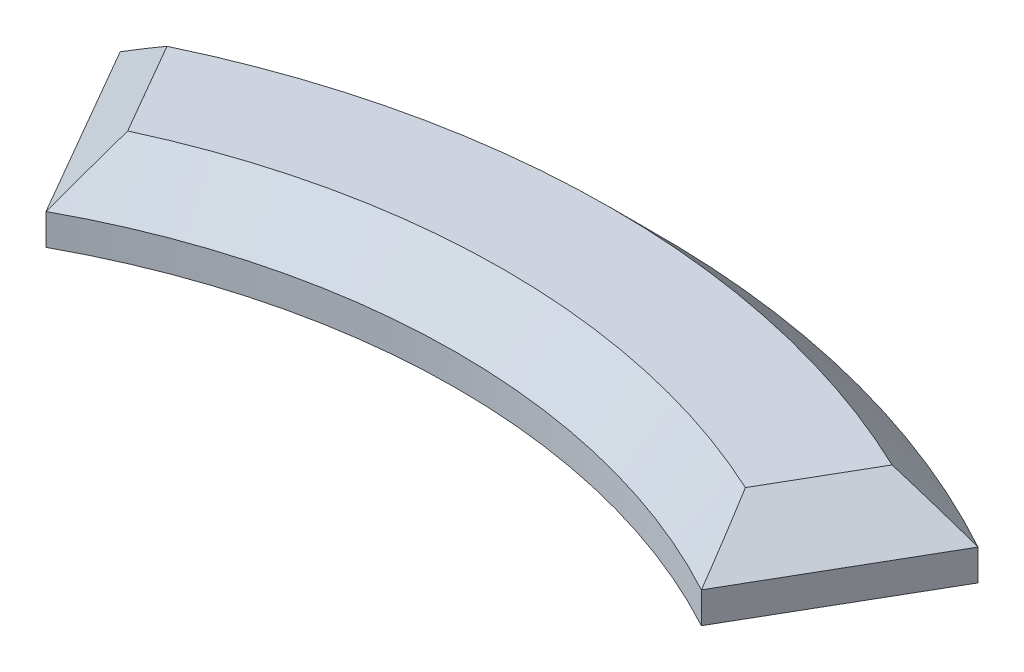
SolidWorks part; units mm, degrees
ref_plane "Front Plane" through (0, 0, 0) normal (0, 0, 1) x (1, 0, 0)
ref_plane "Top Plane" through (0, 0, 0) normal (0, 1, 0) x (1, 0, 0)
ref_plane "Right Plane" through (0, 0, 0) normal (1, 0, 0) x (0, 0, -1)
sketch "Sketch1" plane through (0, 0, 0) normal (0, 1, 0) x (1, 0, 0)
  line L0 (-14, 24.2487) -> (-19, 32.909) construction
  line L1 (14, 24.2487) -> (19, 32.909) construction
  line L2 (0, 0) -> (4, 0) construction
  line L3 (-17.9717, 32.6279) -> (-13.7293, 25.2798)
  line L4 (17.9717, 32.6279) -> (13.7293, 25.2798)
  line L5 (-16.5, 28.5788) -> (-15.8505, 28.9538) construction
  line L6 (15.8505, 28.9538) -> (16.5, 28.5788) construction
  circle A0 centre (0, 0) radius 28 construction
  circle A1 centre (0, 0) radius 38 construction
  arc A2 (-17.9717, 32.6279) -> (17.9717, 32.6279) centre (0, 0) cw
  arc A3 (-13.7293, 25.2798) -> (13.7293, 25.2798) centre (0, 0) cw
  point P19 (16.5, 28.5788)
  dimension "D1" = 28
  dimension "D2" = 38
  dimension "D4" = 0.75
  dimension "D6" = 60
  dimension "D3" = 60
  dimension "D5" = 0.75
extrude "Boss-Extrude1" add sketch "Sketch1" along normal blind 3.3
chamfer "Chamfer1" distance 2 angle 45 4 edges at (15.8505, 3.3, -28.9538) (0, 3.3, -37.25) (0, 3.3, -28.7673) (-15.8505, 3.3, -28.9538)
sketch "Sketch2" plane through (0, 0, 0) normal (0, -1, 0) x (1, 0, 0)
  line L0 (13.7293, -25.2798) -> (17.9717, -32.6279) construction
  line L3 (-17.9717, -32.6279) -> (-13.7293, -25.2798) construction
  circle A2 centre (0, -33) radius 1.625
  arc A3 (-15.8462, -28.9465) -> (15.8462, -28.9465) centre (0, 0) ccw construction
  point P0 (-14.5783, -26.7504)
  dimension "D1" = 3.25
  dimension "D2" = 33
extrude "Cut-Extrude1" cut sketch "Sketch2" against normal blind 2
